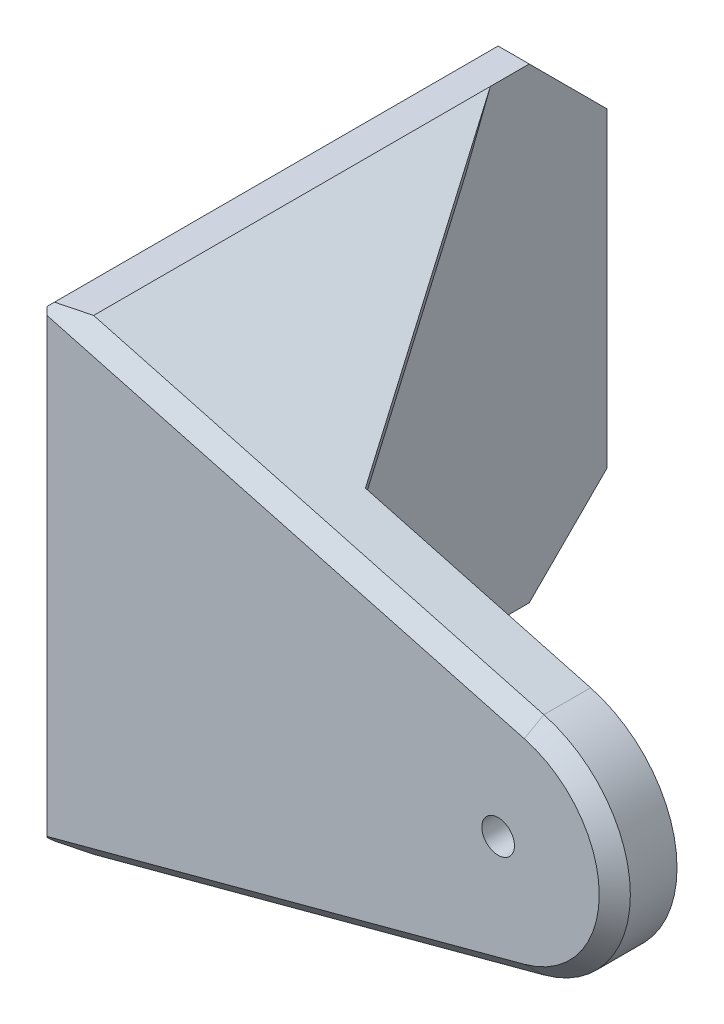
SolidWorks part; units mm, degrees
ref_plane "Front Plane" through (0, 0, 0) normal (0, 0, 1) x (1, 0, 0)
ref_plane "Top Plane" through (0, 0, 0) normal (0, 1, 0) x (1, 0, 0)
ref_plane "Right Plane" through (0, 0, 0) normal (1, 0, 0) x (0, 0, -1)
sketch "Sketch1" plane through (0, 0, 0) normal (0, 0, 1) x (1, 0, 0)
  line L0 (-24.444, 5.5562) -> (-24.444, -9.4438)
  line L1 (5.556, 5.5562) -> (-24.444, 5.5562) construction
  line L2 (-24.444, 5.5562) -> (-24.444, 20.5562)
  line L3 (-24.444, -9.4438) -> (-21.444, -9.4438)
  line L4 (-21.444, -9.4438) -> (7.4973, -1.6881)
  line L5 (-24.444, 20.5562) -> (-21.444, 20.5562)
  line L6 (-21.444, 20.5562) -> (7.4973, 12.8006)
  circle A1 centre (5.556, 5.5562) radius 1.984
  circle A2 centre (5.556, 5.5562) radius 7.5
  dimension "D1" = 15
  dimension "D2" = 30
  dimension "D3" = 15
  dimension "D4" = 15
  dimension "D5" = 3
  dimension "D6" = 3
extrude "Boss-Extrude1" add sketch "Sketch1" along normal blind 4 contours A2 L1 L0 L3 L4 | L1 A2 L6 L5 L2 | A1 A2 | A1 region at (-13.0294, -0.9504, 0) region at (-13.0294, 12.0629, 0) region at (5.556, 7.4841, 0) region at (1.1195, 11.3382, 0)
extrude "Cut-Extrude1" cut sketch "Sketch1<3>" along normal blind 1 contours A1
sketch "Sketch1<3>" plane through (0, 0, 0) normal (0, 0, 1) x (1, 0, 0) same geometry as "Sketch1"
sketch "Sketch2" plane through (0, 0, 4) normal (0, 0, 1) x (1, 0, 0)
  circle A0 centre (5.556, 5.5562) radius 1.984 construction
  circle A1 centre (5.556, 5.5562) radius 1.984
  circle A2 centre (5.556, 5.5562) radius 1.05
  dimension "D1" = 2.1
extrude "Cut-Extrude2" cut sketch "Sketch2" against normal up to next contours A2 region at (5.556, 5.5562, 4)
sketch "Sketch3" plane through (0, 0, 0) normal (0, 0, -1) x (-1, 0, 0)
  line L0 (21.444, 20.5562) -> (21.444, -9.4438)
  line L1 (21.444, -9.4438) -> (24.444, -9.4438)
  line L2 (24.444, -9.4438) -> (24.444, 20.5562)
  line L3 (24.444, 20.5562) -> (21.444, 20.5562)
extrude "Boss-Extrude2" add sketch "Sketch3" along normal blind 30
sketch "Sketch4" plane through (3.7028, 13.8175, 0) normal (0.2588, 0.9659, 0) x (0.9659, -0.2588, 0)
  line L0 (-26.034, 22.5) -> (-11.0528, 0)
  line L1 (-26.034, 0) -> (3.9284, 0) construction
  line L3 (-26.034, 15) -> (-26.034, 30) construction
  line L4 (-26.034, 30) -> (-26.034, 0) construction
  line L5 (-11.0528, 0) -> (-11.0528, -0.5)
  line L6 (-11.0528, -0.5) -> (-26.034, -0.5)
  line L7 (-26.034, -4) -> (-26.034, 0) construction
  line L8 (-26.034, -0.5) -> (-26.034, 22.5)
  dimension "D1" = 0.5
extrude "Boss-Extrude3" add sketch "Sketch4" against normal blind 4
ref_axis "Axis1" through (5.556, 5.5562, 0) along (-1, 0, 0)
ref_plane "Plane1" through (0, 5.5562, 0) normal (0, 1, 0) x (-1, 0, 0)
chamfer "Chamfer1" distance 5 angle 45 1 edges at (-21.444, 3.4857, 0)
chamfer "Chamfer2" distance 5 angle 45 2 edges at (-22.944, -9.4438, -30) (-22.944, 20.5562, -30)
chamfer "Chamfer3" distance 1 angle 45 9 edges at (-24.444, 18.0562, -27.5) (-24.444, 20.5562, -10.5) (-24.444, 5.5562, 4) (-24.444, -9.4438, -10.5) (-24.444, -6.9438, -27.5) (-24.444, 5.5562, -30) (-6.9733, -5.5659, 4) (13.056, 5.5562, 4) (-6.9733, 16.6784, 4)
